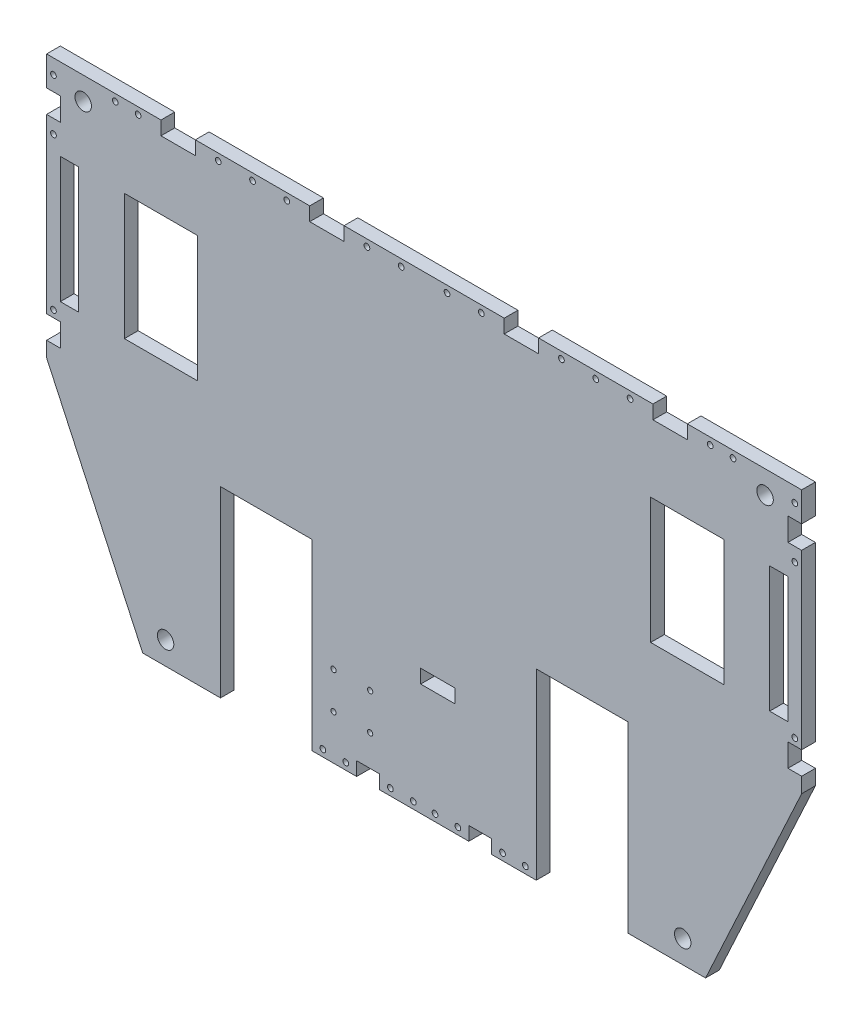
SolidWorks part; units mm, degrees
ref_plane "Plan de face" through (0, 0, 0) normal (0, 0, 1) x (1, 0, 0)
ref_plane "Plan de dessus" through (0, 0, 0) normal (0, 1, 0) x (1, 0, 0)
ref_plane "Plan de droite" through (0, 0, 0) normal (1, 0, 0) x (0, 0, -1)
sketch "Esquisse1" plane through (0, 0, 0) normal (0, 0, 1) x (1, 0, 0)
  line L0 (0, 124.9429) -> (0, -204.46) construction
  line L1 (-165, 96.73) -> (165, 96.73)
  line L2 (165, 96.73) -> (165, -18.27)
  line L3 (165, -18.27) -> (123, -109.0224)
  line L4 (123, -109.0224) -> (-123, -109.0224)
  line L5 (-211.9802, 0) -> (248.5953, 0) construction
  line L6 (-123, -109.0224) -> (-165, -18.27)
  line L7 (-165, -18.27) -> (-165, 96.73)
  line L9 (13.5, -54.0224) -> (-1.5, -54.0224)
  line L10 (13.5, -54.0224) -> (13.5, -60.0224)
  line L11 (13.5, -60.0224) -> (-1.5, -60.0224)
  line L12 (-1.5, -54.0224) -> (-1.5, -60.0224)
  circle A0 centre (-23.6, -89.5224) radius 1.15
  circle A1 centre (-23.6, -73.5224) radius 1.15
  circle A2 centre (-39.6, -89.5224) radius 1.15
  circle A3 centre (-39.6, -73.5224) radius 1.15
  dimension "D15" = 2.3
  dimension "D16" = 2.3
  dimension "D17" = 2.3
  dimension "D18" = 2.3
  dimension "D24" = 83.4
  dimension "D2" = 165
  dimension "D3" = 330
  dimension "D4" = 100
  dimension "D5" = 115
  dimension "D6" = 100
  dimension "D7" = 246
  dimension "D8" = 205.7524
  dimension "D9" = 96.73
  dimension "D10" = 115
  dimension "D11" = 6
  dimension "D12" = 15
  dimension "D13" = 49
  dimension "D14" = 109.5
  dimension "D19" = 19.5
  dimension "D20" = 16
  dimension "D21" = 16
  dimension "D22" = 16
  dimension "D23" = 16
extrude "Boss.-Extru.1" add sketch "Esquisse1" along normal blind 6
sketch "Esquisse2" plane through (0, 0, 6) normal (0, 0, 1) x (1, 0, 0)
  line L0 (-123, -109.0224) -> (123, -109.0224) construction
  line L1 (-159, 60.9776) -> (-151, 60.9776)
  line L2 (-159, 60.9776) -> (-159, 5.9776)
  line L3 (-159, 5.9776) -> (-151, 5.9776)
  line L4 (-151, 60.9776) -> (-151, 5.9776)
  line L5 (-131, 60.9776) -> (-99, 60.9776)
  line L6 (-131, 60.9776) -> (-131, 5.9776)
  line L7 (-131, 5.9776) -> (-99, 5.9776)
  line L8 (-99, 60.9776) -> (-99, 5.9776)
  line L9 (0, 145.0258) -> (0, -189.2208) construction
  line L10 (99, 60.9776) -> (99, 5.9776)
  line L11 (131, 5.9776) -> (99, 5.9776)
  line L12 (131, 60.9776) -> (131, 5.9776)
  line L13 (131, 60.9776) -> (99, 60.9776)
  line L14 (151, 60.9776) -> (151, 5.9776)
  line L15 (159, 5.9776) -> (151, 5.9776)
  line L16 (159, 60.9776) -> (159, 5.9776)
  line L17 (159, 60.9776) -> (151, 60.9776)
  line L19 (89, -109.0224) -> (89, -29.0224)
  line L20 (-49, -109.0224) -> (-89, -109.0224)
  line L21 (-49, -109.0224) -> (-49, -29.0224)
  line L22 (-49, -29.0224) -> (-89, -29.0224)
  line L23 (-89, -109.0224) -> (-89, -29.0224)
  line L24 (49, -29.0224) -> (89, -29.0224)
  line L25 (49, -109.0224) -> (49, -29.0224)
  line L26 (49, -109.0224) -> (89, -109.0224)
  line L27 (-165, 96.73) -> (-165, -18.27) construction
  line L28 (-123, -109.0224) -> (123, -109.0224) construction
  line L29 (165, -18.27) -> (165, 96.73) construction
  line L30 (165, 96.73) -> (-165, 96.73) construction
  circle A0 centre (149, 86.73) radius 3.6
  circle A1 centre (113, -99.0224) radius 3.6
  circle A2 centre (-149, 86.73) radius 3.6
  circle A3 centre (-113, -99.0224) radius 3.6
  point P42 (145.6144, 87.0255)
  dimension "D16" = 7.2
  dimension "D17" = 7.2
  dimension "D18" = 10
  dimension "D19" = 10
  dimension "D20" = 16
  dimension "D21" = 10
  dimension "D2" = 8
  dimension "D3" = 20
  dimension "D4" = 32
  dimension "D5" = 99
  dimension "D6" = 55
  dimension "D7" = 55
  dimension "D8" = 115
  dimension "D9" = 115
  dimension "D10" = 40
  dimension "D11" = 80
  dimension "D12" = 76
  dimension "D13" = 98
  dimension "D14" = 6
  dimension "D15" = 0
extrude "Enlèv. mat.-Extru.1" cut sketch "Esquisse2" against normal blind 6
sketch "Esquisse3" plane through (0, 0, 0) normal (0, 0, -1) x (-1, 0, 0)
  line L0 (165, 96.73) -> (165, -18.27) construction
  line L1 (165, -11.645) -> (159, -11.645)
  line L2 (165, -11.645) -> (165, -1.645)
  line L3 (165, -1.645) -> (159, -1.645)
  line L4 (159, -11.645) -> (159, -1.645)
  line L5 (49, -109.0224) -> (-49, -109.0224) construction
  line L6 (165, 73.8526) -> (159, 73.8526)
  line L7 (165, 73.8526) -> (165, 83.8526)
  line L8 (165, 83.8526) -> (159, 83.8526)
  line L9 (159, 73.8526) -> (159, 83.8526)
  line L10 (29.5, -109.0224) -> (19.5, -109.0224)
  line L11 (29.5, -109.0224) -> (29.5, -103.0224)
  line L12 (29.5, -103.0224) -> (19.5, -103.0224)
  line L13 (19.5, -109.0224) -> (19.5, -103.0224)
  line L14 (49, -109.0224) -> (49, -29.0224) construction
  line L15 (0, -209.4812) -> (0, 177.1799) construction
  line L17 (151, 60.9776) -> (159, 60.9776) construction
  line L18 (-19.5, -109.0224) -> (-19.5, -103.0224)
  line L19 (-29.5, -103.0224) -> (-19.5, -103.0224)
  line L20 (-29.5, -109.0224) -> (-29.5, -103.0224)
  line L21 (-29.5, -109.0224) -> (-19.5, -109.0224)
  line L22 (-159, 73.8526) -> (-159, 83.8526)
  line L23 (-165, 83.8526) -> (-159, 83.8526)
  line L24 (-165, 73.8526) -> (-165, 83.8526)
  line L25 (-165, 73.8526) -> (-159, 73.8526)
  line L26 (-159, -11.645) -> (-159, -1.645)
  line L27 (-165, -1.645) -> (-159, -1.645)
  line L28 (-165, -11.645) -> (-165, -1.645)
  line L29 (-165, -11.645) -> (-159, -11.645)
  line L30 (-165, 96.73) -> (165, 96.73) construction
  line L31 (115, 96.73) -> (100, 96.73)
  line L32 (115, 96.73) -> (115, 90.73)
  line L33 (115, 90.73) -> (100, 90.73)
  line L34 (100, 96.73) -> (100, 90.73)
  line L35 (-35, 96.73) -> (-35, 90.73)
  line L36 (50, 96.73) -> (35, 96.73)
  line L37 (50, 96.73) -> (50, 90.73)
  line L38 (50, 90.73) -> (35, 90.73)
  line L39 (35, 96.73) -> (35, 90.73)
  line L40 (-50, 90.73) -> (-35, 90.73)
  line L41 (-50, 96.73) -> (-50, 90.73)
  line L42 (-50, 96.73) -> (-35, 96.73)
  line L43 (-100, 96.73) -> (-100, 90.73)
  line L44 (-115, 90.73) -> (-100, 90.73)
  line L45 (-115, 96.73) -> (-115, 90.73)
  line L46 (-115, 96.73) -> (-100, 96.73)
  dimension "D1" = 10
  dimension "D2" = 6
  dimension "D3" = 6
  dimension "D4" = 10
  dimension "D5" = 10
  dimension "D6" = 6
  dimension "D7" = 19.5
  dimension "D8" = 6.625
  dimension "D9" = 12.875
  dimension "D10" = 15
  dimension "D11" = 15
  dimension "D12" = 50
  dimension "D13" = 50
  dimension "D14" = 6
extrude "Enlèv. mat.-Extru.2" cut sketch "Esquisse3" against normal blind 6
sketch "Esquisse4" plane through (0, 0, 0) normal (0, 0, -1) x (-1, 0, 0)
  line L0 (159, 73.8526) -> (165, 73.8526) construction
  line L2 (54.0695, -106.0224) -> (4.75, -106.0224) construction
  line L3 (49, -109.0224) -> (29.5, -109.0224) construction
  line L4 (49, -109.0224) -> (49, -29.0224) construction
  line L5 (19.5, -103.0224) -> (19.5, -109.0224) construction
  line L6 (115, 96.73) -> (165, 96.73) construction
  line L8 (165, 73.8526) -> (165, -1.645) construction
  line L10 (165, 96.73) -> (165, 83.8526) construction
  line L11 (143.8632, 93.73) -> (10, 93.73) construction
  line L12 (50, 96.73) -> (100, 96.73) construction
  line L13 (115, 90.73) -> (115, 96.73) construction
  line L14 (100, 96.73) -> (100, 90.73) construction
  line L15 (50, 90.73) -> (50, 96.73) construction
  line L16 (35, 96.73) -> (35, 90.73) construction
  line L17 (0, 142.2997) -> (0, -202.2086) construction
  line L18 (-143.8632, 93.73) -> (-10, 93.73) construction
  line L19 (-54.0695, -106.0224) -> (-4.75, -106.0224) construction
  line L21 (165, -1.645) -> (159, -1.645) construction
  circle A0 centre (162, 1.355) radius 1.25
  circle A2 centre (162, 67.8526) radius 1.25
  circle A5 centre (162, 90.29) radius 1.25
  circle A6 centre (44.25, -106.0224) radius 1.25
  circle A7 centre (14.75, -106.0224) radius 1.25
  circle A8 centre (4.75, -106.0224) radius 1.25
  circle A9 centre (34.2497, -106.0224) radius 1.25
  circle A10 centre (135, 93.73) radius 1.25
  circle A11 centre (125, 93.73) radius 1.25
  circle A12 centre (90, 93.73) radius 1.25
  circle A13 centre (75, 93.73) radius 1.25
  circle A14 centre (60, 93.73) radius 1.25
  circle A15 centre (25, 93.73) radius 1.25
  circle A16 centre (10, 93.73) radius 1.25
  circle A17 centre (-10, 93.73) radius 1.25
  circle A18 centre (-25, 93.73) radius 1.25
  circle A19 centre (-60, 93.73) radius 1.25
  circle A20 centre (-75, 93.73) radius 1.25
  circle A21 centre (-90, 93.73) radius 1.25
  circle A22 centre (-125, 93.73) radius 1.25
  circle A23 centre (-135, 93.73) radius 1.25
  circle A24 centre (-34.2497, -106.0224) radius 1.25
  circle A25 centre (-4.75, -106.0224) radius 1.25
  circle A26 centre (-14.75, -106.0224) radius 1.25
  circle A27 centre (-44.25, -106.0224) radius 1.25
  circle A28 centre (-162, 90.29) radius 1.25
  circle A31 centre (-162, 67.8526) radius 1.25
  circle A33 centre (-162, 1.355) radius 1.25
  dimension "D1" = 2.5
  dimension "D3" = 2.5
  dimension "D10" = 2.5
  dimension "D11" = 2.5
  dimension "D12" = 2.5
  dimension "D13" = 2.5
  dimension "D14" = 10.0003
  dimension "D18" = 3
  dimension "D19" = 2.5
  dimension "D29" = 2.5
  dimension "D30" = 2.5
  dimension "D31" = 2.5
  dimension "D32" = 2.5
  dimension "D33" = 2.5
  dimension "D34" = 2.5
  dimension "D35" = 2.5
  dimension "D40" = 10
  dimension "D5" = 3
  dimension "D6" = 6
  dimension "D7" = 6.44
  dimension "D9" = 3
  dimension "D15" = 4.75
  dimension "D16" = 10
  dimension "D17" = 4.75
  dimension "D24" = 3
  dimension "D26" = 3
  dimension "D28" = 3
  dimension "D36" = 10
  dimension "D37" = 10
  dimension "D38" = 10
  dimension "D39" = 15
  dimension "D41" = 15
  dimension "D42" = 10
extrude "Enlèv. mat.-Extru.3" cut sketch "Esquisse4" against normal blind 6
